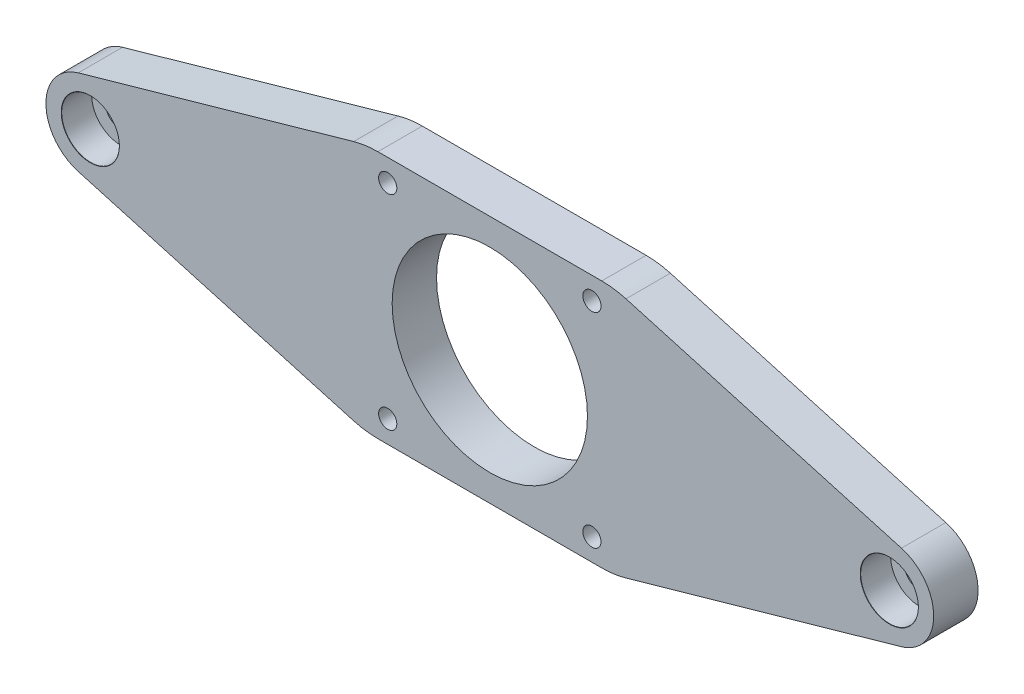
SolidWorks part; units mm, degrees
material "ABS PC"
ref_plane "Front Plane" through (0, 0, 0) normal (0, 0, 1) x (1, 0, 0)
ref_plane "Top Plane" through (0, 0, 0) normal (0, 1, 0) x (1, 0, 0)
ref_plane "Right Plane" through (0, 0, 0) normal (1, 0, 0) x (0, 0, -1)
sketch "Sketch1" plane through (0, 0, 0) normal (0, 0, 1) x (1, 0, 0)
  line L0 (0, 11) -> (0, 14)
  line L1 (-46.3657, 4.8099) -> (-14, 14)
  line L2 (-11, 0) -> (-45, 0)
  line L3 (-14, 14) -> (0, 14)
  line L4 (-14, 14) -> (-14, 0) construction
  line L5 (-45, 0) -> (-50, 0)
  line L6 (0, 0) -> (0, 11) construction
  arc A0 (-50, 0) -> (-46.3657, 4.8099) centre (-45, 0) cw
  arc A1 (-11, 0) -> (0, 11) centre (0, 0) cw
  dimension "D3" = 5
  dimension "D4" = 11
  dimension "D1" = 14
  dimension "D2" = 45
extrude "Boss-Extrude1" add sketch "Sketch1" along normal blind 5 contours L1 L3 L0 A1 L2 L5 A0
fillet "Fillet1" radius 10 1 edges at (-14, 14, 2.5)
mirror "Mirror1" about plane through (-45, 0, 5) normal (0, -1, 0) of bodies 101
mirror "Mirror2" about plane through (0, -11, 5) normal (-1, 0, 0) of bodies 102
hole_wizard "CBORE for M3 Hex Socket Head Cap Screw1" positions "Sketch2" profile "Sketch4" counterbore size "M3" standard "ISO"
sketch "Sketch2" plane through (0, 0, 5) normal (0, 0, 1) x (1, 0, 0)
  point P0 (-45, 0)
  point P3 (45, 0)
sketch "Sketch4" plane through (-45, 0, 5) normal (1, 0, 0) x (0, -1, 0)
  line L0 (0, 0) -> (0, 12.5215)
  line L1 (0, 12.5215) -> (1.7, 11.5)
  line L2 (1.7, 11.5) -> (1.7, 3.4)
  line L3 (1.7, 3.4) -> (3.25, 3.4)
  line L5 (3.25, 3.4) -> (3.25, 0.025)
  line L6 (3.25, 0.025) -> (3.275, 0)
  line L7 (3.275, 0) -> (0, 0)
  line L8 (-3.25, 0.025) -> (-3.275, 0) construction
  line L10 (0, 12.5215) -> (-1.7, 11.5) construction
  line L11 (0, -6.35) -> (0, 107.95) construction
  dimension "Hole Dia." = 3.4
  dimension "Hole Depth" = 11.5
  dimension "C'Bore Dia." = 6.5
  dimension "C'Bore Depth" = 3.4
  dimension "Near C'Sink Dia." = 6.55
  dimension "Near C'Sink Angle" = 90
  dimension "Drill Angle" = 118
hole_wizard "M2.5 Tapped Hole1" positions "Sketch5" profile "Sketch6" tap size "M2.5" standard "ISO"
sketch "Sketch5" plane through (0, 0, 5) normal (0, 0, 1) x (1, 0, 0)
  line L1 (-11.5, 11.5) -> (11.5, 11.5) construction
  line L2 (-11.5, 11.5) -> (-11.5, -11.5) construction
  line L3 (-11.5, -11.5) -> (11.5, -11.5) construction
  line L4 (11.5, 11.5) -> (11.5, -11.5) construction
  line L5 (0, 0) -> (0, 11.5) construction
  line L7 (0, 0) -> (11.5, 0) construction
  point P0 (-11.5, 11.5)
  point P2 (11.5, 11.5)
  point P4 (11.5, -11.5)
  point P6 (-11.5, -11.5)
  dimension "D1" = 23
cosmetic thread "Hole Thread1" parameters "D1"=5, "D2"=2.5
cosmetic thread "Hole Thread2" parameters "D1"=5, "D2"=2.5
cosmetic thread "Hole Thread3" parameters "D1"=5, "D2"=2.5
cosmetic thread "Hole Thread4" parameters "D1"=5, "D2"=2.5
sketch "Sketch6" plane through (-11.5, 11.5, 5) normal (1, 0, 0) x (0, -1, 0)
  line L0 (0, 0) -> (0, 6.9659)
  line L1 (0, 6.9659) -> (1.025, 6.35)
  line L2 (1.025, 6.35) -> (1.025, 0)
  line L5 (1.025, 0) -> (0, 0)
  line L10 (0, 6.9659) -> (-1.025, 6.35) construction
  line L11 (0, -6.35) -> (0, 107.95) construction
  dimension "Tap Drill Dia." = 2.05
  dimension "Tap Drill Depth" = 6.35
  dimension "Drill Angle" = 118
